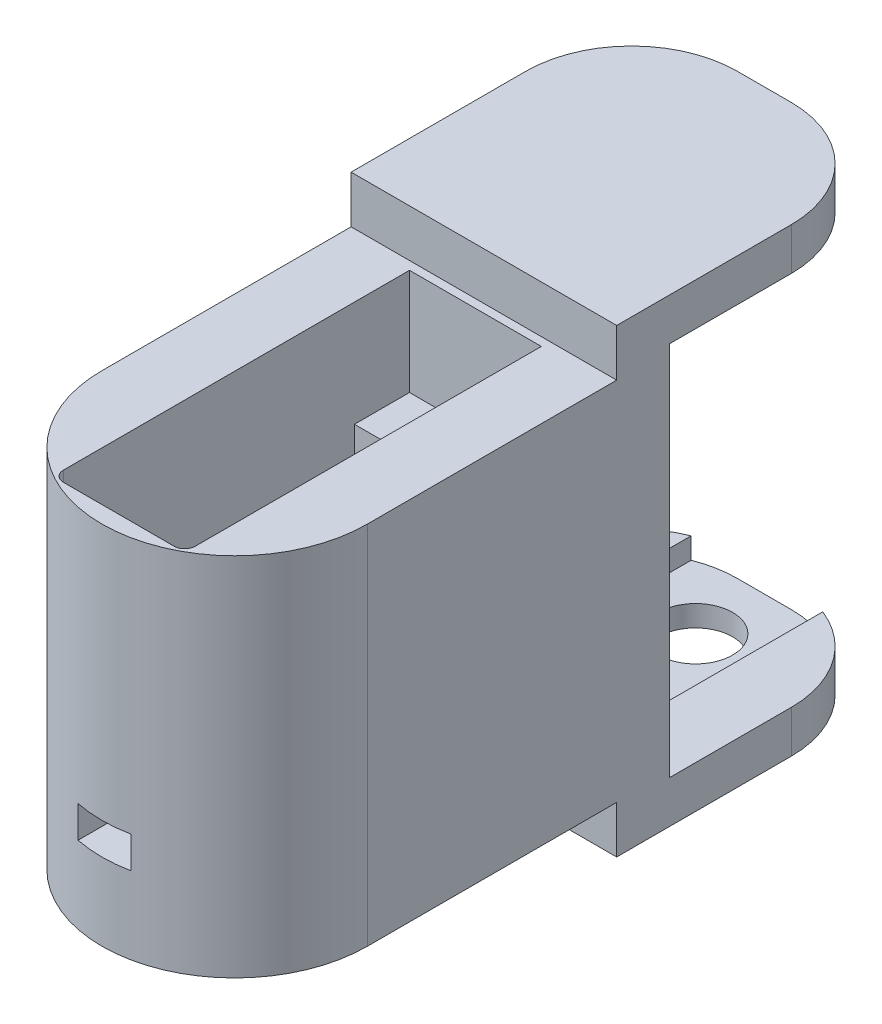
SolidWorks part; units mm, degrees
ref_plane "Front Plane" through (0, 0, 0) normal (0, 0, 1) x (1, 0, 0)
ref_plane "Top Plane" through (0, 0, 0) normal (0, 1, 0) x (1, 0, 0)
ref_plane "Right Plane" through (0, 0, 0) normal (1, 0, 0) x (0, 0, -1)
sketch "Sketch4" plane through (0, 0, 0) normal (0, 0, 1) x (1, 0, 0)
  line L1 (-6.23, -9.975) -> (6.23, -9.975)
  line L2 (-6.23, -9.975) -> (-6.23, 7.275)
  line L3 (-6.23, 7.275) -> (6.23, 7.275)
  line L4 (6.23, -9.975) -> (6.23, 7.275)
  point P4 (0, 7.275)
  dimension "D1" = 12.46
  dimension "D2" = 17.25
  dimension "D3" = 9.975
extrude "Boss-Extrude3" add sketch "Sketch4" along normal blind 6
sketch "Sketch8" plane through (0, -9.975, 0) normal (0, -1, 0) x (-1, 0, 0)
  circle A0 centre (0, -23.55) radius 12.5468
  circle A1 centre (0, -23.55) radius 11.15
  dimension "D1" = 22.3
  dimension "D2" = 23.55
extrude "Boss-Extrude6" add sketch "Sketch8" along normal blind 7.3 and the other way up to surface (17.25 mm away) other way up to face at (0, 7.275, 3)
sketch "Sketch5" plane through (0, 7.275, 0) normal (0, 1, 0) x (1, 0, 0)
  line L8 (12.5468, -23.55) -> (12.5468, 0)
  line L9 (12.5468, 0) -> (6.23, 0)
  line L10 (-12.5468, -23.55) -> (-12.5468, 0)
  line L11 (-12.5468, 0) -> (-6.23, 0)
  line L12 (-6.23, 0) -> (-6.23, -29.7)
  line L14 (6.23, -29.7) -> (6.23, 0)
  line L15 (-6.23, -29.7) -> (6.23, -29.7)
  line L16 (6.23, -6) -> (-6.23, -6) construction
  circle A0 centre (0, -23.55) radius 12.5468 construction
  arc A1 (-12.5468, -23.55) -> (12.5468, -23.55) centre (0, -23.55) ccw
  dimension "D1" = 23.7
  dimension "D2" = 23.55
extrude "Boss-Extrude4" add sketch "Sketch5" against normal up to surface (17.25 mm away) up to face at (0, -9.975, 3)
sketch "Sketch6" plane through (0, 7.275, 0) normal (0, 1, 0) x (1, 0, 0)
  line L0 (6.23, -6) -> (-6.23, -6) construction
  line L3 (6.23, -29.7) -> (-6.23, -29.7) construction
  circle A0 centre (0, -3.6) radius 0.5
  circle A1 centre (0, -32.1) radius 0.5
  dimension "D1" = 1
  dimension "D3" = 1
  dimension "D2" = 2.4
  dimension "D4" = 2.4
extrude "Cut-Extrude1" cut sketch "Sketch6" against normal blind 5
chamfer "Chamfer1" distance 0.5 angle 60 2 edges at (0, 7.275, 4.1) (0, 7.275, 32.6) first distance on face at (0, 7.275, 4.1)
sketch "Sketch10" plane through (0, 7.275, 0) normal (0, 1, 0) x (1, 0, 0)
  line L1 (-6.23, -6) -> (6.23, -6)
  line L2 (-6.23, -6) -> (-6.23, -29.7)
  line L3 (-6.23, -29.7) -> (6.23, -29.7)
  line L4 (6.23, -6) -> (6.23, -29.7)
extrude "Cut-Extrude3" cut sketch "Sketch10" against normal up to surface (17.25 mm away) up to face at (0, -9.975, 27.1007)
ref_plane "Plane1" through (0, 0, 36.0968) normal (0, 0, 1) x (1, 0, 0)
sketch "Sketch11" plane through (0, 0, 36.0968) normal (0, 0, 1) x (1, 0, 0)
  line L0 (-11.15, -9.975) -> (11.15, -9.975) construction
  line L1 (-2.5, -6.975) -> (2.5, -6.975)
  line L2 (-2.5, -6.975) -> (-2.5, -9.975)
  line L3 (-2.5, -9.975) -> (2.5, -9.975)
  line L4 (2.5, -6.975) -> (2.5, -9.975)
  point P4 (0, -6.975)
  dimension "D1" = 0
  dimension "D2" = 5
  dimension "D3" = 3
extrude "Cut-Extrude4" cut sketch "Sketch11" against normal up to next
sketch "Sketch13" plane through (0, -17.275, 0) normal (0, -1, 0) x (1, 0, 0)
  line L0 (-12.5468, 23.55) -> (-12.5468, 0)
  line L1 (-12.5468, 0) -> (12.5468, 0)
  line L2 (12.5468, 0) -> (12.5468, 23.55)
  arc A0 (-12.5468, 23.55) -> (12.5468, 23.55) centre (0, 23.55) ccw
  point P3 (0, 0)
extrude "Boss-Extrude7" add sketch "Sketch13" against normal up to surface (7.3 mm away) up to face at (6.0145, -9.975, 27.3356)
sketch "Sketch15" plane through (0, 7.275, 0) normal (0, 1, 0) x (1, 0, 0)
  line L0 (-12.5468, 0) -> (12.5468, 0)
  line L1 (12.5468, 0) -> (12.5468, -23.55)
  line L2 (-12.5468, 0) -> (-12.5468, -23.55)
  line L3 (6.23, -6) -> (6.23, -29.7) construction
  line L4 (-6.23, -0.8) -> (6.23, -0.8)
  line L5 (-6.23, -0.8) -> (-6.23, -33.5)
  line L6 (-5.23, -34.5) -> (5.23, -34.5)
  line L7 (6.23, -0.8) -> (6.23, -33.5)
  arc A0 (-12.5468, -23.55) -> (12.5468, -23.55) centre (0, -23.55) ccw
  circle A1 centre (0, -3.6) radius 0.5 construction
  arc A2 (5.23, -34.5) -> (6.23, -33.5) centre (5.23, -33.5) ccw
  arc A3 (-6.23, -33.5) -> (-5.23, -34.5) centre (-5.23, -33.5) ccw
  point P15 (0, -0.8)
  dimension "D1" = 0.8
  dimension "D3" = 1
  dimension "D2" = 2.8
  dimension "D4" = 0
  dimension "D5" = 34.5
extrude "Boss-Extrude9" add sketch "Sketch15" along normal blind 10
sketch "Sketch20" plane through (0, -17.275, 0) normal (0, -1, 0) x (1, 0, 0)
  circle A0 centre (0, 23.55) radius 7.15
  circle A1 centre (0, 23.55) radius 11.15
  circle A2 centre (0, 23.55) radius 11.15 construction
  dimension "D1" = 14.3
extrude "Boss-Extrude11" add sketch "Sketch20" against normal up to surface (7.3 mm away) up to face at (-6.0145, -9.975, 27.3356)
sketch "Sketch21" plane through (0, -17.275, 0) normal (0, -1, 0) x (1, 0, 0)
  circle A0 centre (0, 23.55) radius 7.15
  circle A1 centre (0, 23.55) radius 10.15
  circle A2 centre (0, 23.55) radius 7.15 construction
  dimension "D1" = 20.3
extrude "Cut-Extrude7" cut sketch "Sketch21" against normal blind 1.3
sketch "Sketch17" plane through (-12.5468, 4.7282, 0) normal (1, 0, 0) x (0, -1, 0)
  line L0 (26.4782, 26.5) -> (26.4782, 0)
  line L1 (26.4782, 0) -> (-17.0218, 0)
  line L2 (-17.0218, 0) -> (-17.0218, 26.5)
  line L3 (-17.0218, 26.5) -> (-13.0218, 26.5)
  line L4 (-13.0218, 26.5) -> (-13.0218, 5)
  line L5 (-13.0218, 5) -> (22.4782, 5)
  line L6 (22.4782, 5) -> (22.4782, 26.5)
  line L7 (22.4782, 26.5) -> (26.4782, 26.5)
  point P2 (4.7282, 5)
  point P10 (4.7282, 0)
  dimension "D1" = 4
  dimension "D2" = 35.5
  dimension "D3" = 0
  dimension "D4" = 26.5
  dimension "D5" = 5
extrude "Boss-Extrude10" add sketch "Sketch17" along normal up to surface (25.0936 mm away) up to face at (12.5468, 0, 11.775)
sketch "Sketch18" plane through (0, -17.75, 0) normal (0, 1, 0) x (0, 0, 1)
  line L0 (-26.5, -12.5468) -> (-26.5, 12.5468) construction
  line L1 (-26.5, 6.2191) -> (-5, 6.2191)
  line L2 (-26.5, 6.2191) -> (-26.5, -6.2191)
  line L3 (-26.5, -6.2191) -> (-5, -6.2191)
  line L4 (-5, 6.2191) -> (-5, -6.2191)
  line L5 (-5, -12.5468) -> (-5, 12.5468) construction
  point P6 (-26.5, 0)
  point P7 (-26.5, 0)
  dimension "D1" = 0
extrude "Cut-Extrude5" cut sketch "Sketch18" against normal blind 2
sketch "Sketch19" plane through (0, -19.75, 0) normal (0, 1, 0) x (0, 0, 1)
  line L0 (-26.5, -12.5468) -> (-26.5, 12.5468) construction
  circle A0 centre (-20, 0) radius 3.5
  dimension "D1" = 7
  dimension "D2" = 6.5
extrude "Cut-Extrude6" cut sketch "Sketch19" against normal through all both and the other way through all
fillet "Fillet1" radius 10 4 edges at (12.5468, -19.75, -26.5) (-12.5468, -19.75, -26.5) (-12.5468, 19.75, -26.5) (12.5468, 19.75, -26.5)
ref_plane "Plane2" through (0, 0, 0) normal (1, 0, 0) x (0, 0, -1)
ref_plane "Plane3" through (0, 0, 0) normal (0, -1, 0) x (-1, 0, 0)
sketch "Sketch22" plane through (0, 21.75, 0) normal (0, 1, 0) x (1, 0, 0)
  circle A0 centre (0, 20) radius 6.5
  dimension "D1" = 13
extrude "Boss-Extrude12" add sketch "Sketch22" against normal blind 5
sketch "Sketch23" plane through (0, 16.75, 0) normal (0, -1, 0) x (1, 0, 0)
  circle A0 centre (0, -20) radius 5.85
  dimension "D1" = 11.7
extrude "Boss-Extrude13" add sketch "Sketch23" along normal blind 5
fillet "Fillet2" radius 1 1 edges at (0, 11.75, -25.85)
